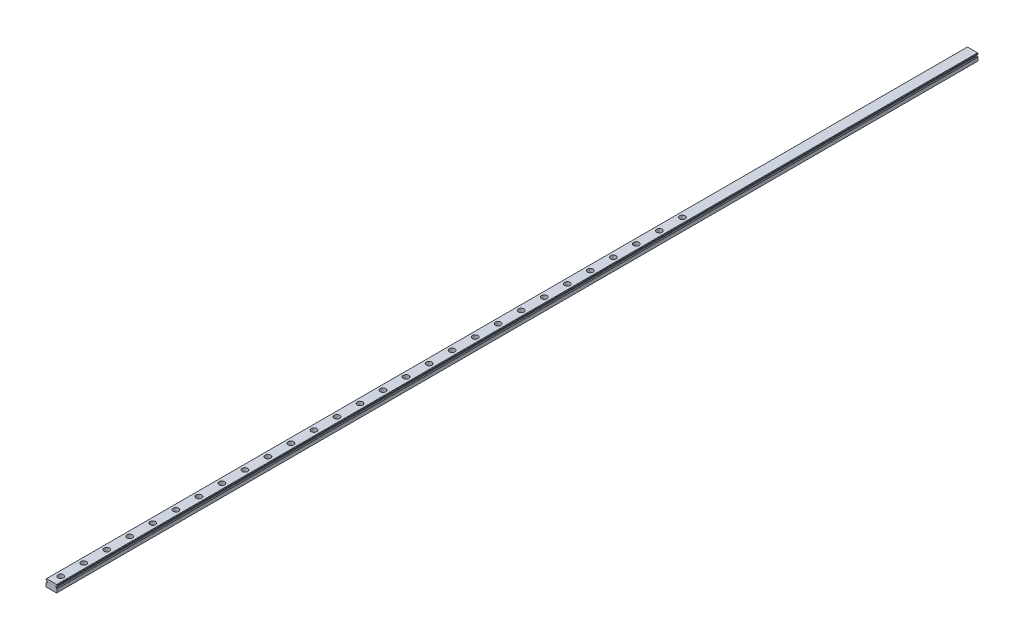
SolidWorks part; units mm, degrees
ref_plane "Front Plane" through (0, 0, 0) normal (0, 0, 1) x (1, 0, 0)
ref_plane "Top Plane" through (0, 0, 0) normal (0, 1, 0) x (1, 0, 0)
ref_plane "Right Plane" through (0, 0, 0) normal (1, 0, 0) x (0, 0, -1)
sketch "Sketch1" plane through (0, 0, 0) normal (0, 0, 1) x (1, 0, 0)
  line L0 (-6, 0) -> (6, 0) construction
  line L1 (0, -4) -> (0, 4) construction
  line L2 (0, 4) -> (0, -4) construction
  line L3 (-3, 4) -> (3, 4) construction
  line L4 (-1.75, -0.5) -> (1.75, -0.5) construction
  point P0 (0, -0.5)
  point P3 (-6, -4)
  point P4 (0, 0)
  point P8 (0, 0)
  point P11 (0, 4)
  point P15 (0, 4)
  point P17 (0, -0.5)
  point P18 (6, 4)
  point P20 (-6, 4)
  dimension "Rail Width" = 12
  dimension "Rail Height" = 8
  dimension "Mounting Hole Depth" = 3.5
  dimension "Mounting Hole Counterbore Diameter" = 6
  dimension "Mounting Hole Diameter" = 3.5
sketch "Sketch2" plane through (0, 0, 0) normal (1, 0, 0) x (0, 0, -1)
  line L0 (500, 0) -> (-500, 0) construction
  line L1 (-14, 4) -> (14, 4) construction
  line L3 (0, 4) -> (0, 0) construction
  point P0 (-490, 0)
  point P4 (0, 0)
  point P5 (-465, 0)
  point P6 (-477.5, 0)
  point P9 (-490, 4)
  point P10 (0, 4)
  point P11 (500, 4)
  point P13 (-500, 4)
  point P14 (477.5, 0)
  point P17 (-500, -4)
  dimension "Rail Length" = 1000
  dimension "Mounting Hole Center to Edge" = 10
  dimension "Mounting Hole Center to Center" = 25
  dimension "Number of Mounting Holes" = 28
  dimension "Break Line" = 12.5
sketch "Sketch3" plane through (0, 0, 0) normal (0, 0, 1) x (1, 0, 0)
  point P0 (0, 4)
  line B0 (-6, 0.1421) -> (-6, -3.5)
  line B1 (-6, -3.5) -> (-5.5, -4)
  line B2 (-5.5, -4) -> (1.6, -4)
  line B3 (2.4, -4) -> (5.5, -4)
  line B4 (5.5, -4) -> (6, -3.5)
  line B5 (6, -3.5) -> (6, 0.1421)
  line B6 (5.0738, 0.9945) -> (4.7282, 1.0247)
  line B7 (4.5, 1.2738) -> (4.5, 1.7262)
  line B8 (4.7282, 1.9753) -> (5.0948, 2.0073)
  line B9 (6, 2.8254) -> (6, 3.5)
  line B10 (6, 3.5) -> (5.5, 4)
  line B11 (5.5, 4) -> (-5.5, 4)
  line B12 (-5.5, 4) -> (-6, 3.5)
  line B13 (-6, 3.5) -> (-6, 2.8254)
  line B14 (-5.0948, 2.0073) -> (-4.7282, 1.9753)
  line B15 (-4.5, 1.7262) -> (-4.5, 1.2738)
  line B16 (-4.7282, 1.0247) -> (-5.0738, 0.9945)
  arc B17 (-5.8448, 0.3734) -> (-6, 0.1421) centre (-5.75, 0.1421) ccw
  arc B18 (2.4, -4) -> (1.6, -4) centre (2, -4.3) ccw
  arc B19 (6, 0.1421) -> (5.8448, 0.3734) centre (5.75, 0.1421) ccw
  arc B20 (5.2672, 0.8728) -> (5.8448, 0.3734) centre (6.3, 1.4838) ccw
  arc B21 (5.2672, 0.8728) -> (5.0738, 0.9945) centre (5.052, 0.7455) ccw
  arc B22 (4.5, 1.2738) -> (4.7282, 1.0247) centre (4.75, 1.2738) ccw
  arc B23 (4.7282, 1.9753) -> (4.5, 1.7262) centre (4.75, 1.7262) ccw
  arc B24 (5.0948, 2.0073) -> (5.2845, 2.1232) centre (5.073, 2.2564) ccw
  arc B25 (5.8448, 2.5941) -> (5.2845, 2.1232) centre (6.3, 1.4838) ccw
  arc B26 (5.8448, 2.5941) -> (6, 2.8254) centre (5.75, 2.8254) ccw
  arc B27 (-6, 2.8254) -> (-5.8448, 2.5941) centre (-5.75, 2.8254) ccw
  arc B28 (-5.2845, 2.1232) -> (-5.8448, 2.5941) centre (-6.3, 1.4838) ccw
  arc B29 (-5.2845, 2.1232) -> (-5.0948, 2.0073) centre (-5.073, 2.2564) ccw
  arc B30 (-4.5, 1.7262) -> (-4.7282, 1.9753) centre (-4.75, 1.7262) ccw
  arc B31 (-4.7282, 1.0247) -> (-4.5, 1.2738) centre (-4.75, 1.2738) ccw
  arc B32 (-5.0738, 0.9945) -> (-5.2672, 0.8728) centre (-5.052, 0.7455) ccw
  arc B33 (-5.8448, 0.3734) -> (-5.2672, 0.8728) centre (-6.3, 1.4838) ccw
sketch_block_instance "12mm Block-1"
sketch_block "12mm Block"
extrude "Boss-Extrude1" add sketch "Sketch3" against normal up to vertex (500 mm away) from vertex up to point (0, 0, -500) starting at point (0, 0, 500)
ref_plane "Plane1" through (0, 0, 490) normal (0, 0, 1) x (1, 0, 0)
sketch "Sketch4" plane through (0, 0, 490) normal (0, 0, 1) x (1, 0, 0)
  line L0 (0, 4) -> (0, -4)
  line L1 (0, -4) -> (-1.75, -4)
  line L3 (-1.75, -4) -> (-1.75, -0.5)
  line L4 (-1.75, -0.5) -> (-3, -0.5)
  line L5 (-3, -0.5) -> (-3, 4)
  line L6 (-3, 4) -> (0, 4)
revolve "Cut-Revolve1" cut sketch "Sketch4" angle 360 about L0
sketch "Sketch6" plane through (0, 0, 0) normal (1, 0, 0) x (0, 0, -1)
  line L0 (-487, -0.5) -> (-493, -0.5) construction
  line L5 (-487, -0.5) -> (-493, -0.5)
  line L17 (-491.75, -0.5) -> (-491.75, -4) construction
  line L18 (-488.25, -4) -> (-488.25, -0.5) construction
  line L32 (-487, -0.5) -> (-487, 4) construction
  line L33 (-493, 4) -> (-493, -0.5) construction
  line L34 (-491.75, -0.5) -> (-491.75, -4)
  line L35 (-488.25, -4) -> (-488.25, -0.5)
  line L36 (-487, -0.5) -> (-487, 4)
  line L37 (-493, 4) -> (-493, -0.5)
  line L38 (0, 4) -> (0, -4) construction
  line L40 (493, 4) -> (493, -0.5)
  line L41 (487, -0.5) -> (487, 4)
  line L42 (488.25, -4) -> (488.25, -0.5)
  line L43 (491.75, -0.5) -> (491.75, -4)
  line L44 (487, -0.5) -> (493, -0.5)
sketch "Sketch7" plane through (0, 0, 0) normal (0, 0, 1) x (1, 0, 0)
  line L0 (3, -0.5) -> (3, 4) construction
  line L1 (-3, 4) -> (-3, -0.5) construction
  line L2 (3, -0.5) -> (3, 4)
  line L3 (-3, 4) -> (-3, -0.5)
  line L4 (1.75, -3.867) -> (1.75, -0.5) construction
  line L11 (1.75, -3.867) -> (1.75, -0.5)
  line L18 (-1.75, -0.5) -> (-1.75, -4) construction
  line L32 (3, -0.5) -> (-3, -0.5) construction
  line L34 (-1.75, -0.5) -> (-1.75, -4)
  line L37 (3, -0.5) -> (-3, -0.5)
pattern_linear "LPattern1" count 28 spacing 25 along (0, 0, -1) of "Cut-Revolve1"
equation "\"D3@LPattern1\"=\"Mounting Hole Center to Center@Sketch2\""
equation "\"D1@LPattern1\"=\"Number of Mounting Holes@Sketch2\""
equation "\"Break Line@Sketch2\"=\"Mounting Hole Center to Center@Sketch2\"/2"
